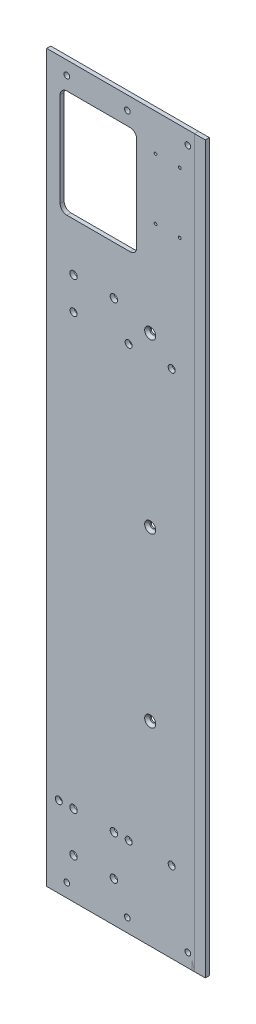
SolidWorks part; units mm, degrees
material "Thornel Mat VMA"
ref_plane "Front" through (0, 0, 0) normal (0, 0, 1) x (1, 0, 0)
ref_plane "Top" through (0, 0, 0) normal (0, 1, 0) x (1, 0, 0)
ref_plane "Right" through (0, 0, 0) normal (1, 0, 0) x (0, 0, -1)
sketch "草图1" plane through (0, 0, 0) normal (0, 0, 1) x (1, 0, 0)
  line L1 (-75, -270) -> (75, -270)
  line L2 (-75, -270) -> (-75, 270)
  line L3 (-75, 270) -> (75, 270)
  line L4 (75, -270) -> (75, 270)
  line L5 (-75, -270) -> (75, 270) construction
  line L6 (-75, 270) -> (75, -270) construction
  point P0 (0, 0)
  dimension "D1" = 150
  dimension "D2" = 540
extrude "凸台-拉伸1" add sketch "草图1" along normal blind 3
sketch "草图2" plane through (0, 0, 0) normal (0, 0, -1) x (-1, 0, 0)
  line L0 (-75, 0) -> (75, 0) construction
  line L1 (-75, -270) -> (-75, 270) construction
  line L2 (75, 270) -> (75, -270) construction
  line L3 (75, -270) -> (-75, -270) construction
  line L4 (0, -270) -> (0, -312.3628) construction
  line L5 (0, 270) -> (0, 297.7999) construction
  line L6 (-75, 270) -> (75, 270) construction
  circle A2 centre (65, -260) radius 2.1
  circle A3 centre (-70, -260) radius 2.1
  circle A6 centre (65, 260) radius 2.1
  circle A7 centre (-70, 260) radius 2.1
  circle A8 centre (-25, -260) radius 2.1
  circle A9 centre (20, -260) radius 2.1
  circle A10 centre (20, 260) radius 2.1
  circle A11 centre (-25, 260) radius 2.1
  circle A16 centre (15, 196.5) radius 1.6
  circle A17 centre (15, 188.5) radius 1.6
  circle A18 centre (-15, 196.5) radius 1.6
  circle A19 centre (-15, 188.5) radius 1.6
  dimension "D2" = 45
  dimension "D3" = 3.2
  dimension "D4" = 4.2
  dimension "D5" = 10
  dimension "D6" = 10
  dimension "D7" = 4.2
  dimension "D8" = 5
  dimension "D9" = 10
  dimension "D10" = 30
  dimension "D11" = 8
  dimension "D12" = 73.5
  dimension "D13" = 45
extrude "切除-拉伸1" cut sketch "草图2" against normal through all
sketch "草图3" plane through (0, 0, 3) normal (0, 0, 1) x (1, 0, 0)
  line L1 (75, -270) -> (75, 270) construction
  circle A0 centre (65, 30) radius 1.5
  circle A1 centre (65, -30) radius 1.5
  dimension "D1" = 3
  dimension "D2" = 10
  dimension "D3" = 30
  dimension "D4" = 3
  dimension "D5" = 30
  dimension "D6" = 10
sketch "草图4" plane through (0, 0, 3) normal (0, 0, 1) x (1, 0, 0)
  line L0 (42, 0) -> (140.7159, 0) construction
  line L1 (75, -270) -> (75, 270) construction
  line L2 (0, 270) -> (0, -270) construction
  line L3 (75, 270) -> (-75, 270) construction
  line L4 (-75, -270) -> (75, -270) construction
  line L5 (-42, 0) -> (-140.7159, 0) construction
  circle A0 centre (42, 125) radius 2.1
  circle A1 centre (42, -125) radius 2.1
  circle A2 centre (42, 0) radius 2.1
  circle A3 centre (-42, 0) radius 2.1
  circle A4 centre (-42, -125) radius 2.1
  circle A5 centre (-42, 125) radius 2.1
  dimension "D1" = 250
  dimension "D2" = 4.2
  dimension "D3" = 4.2
  dimension "D4" = 33
  dimension "D5" = 33
extrude "切除-拉伸2" cut sketch "草图4" against normal up to next
chamfer "倒角1" distance 2 angle 45 3 edges at (44.1, 0, 3) (39.9, -125, 3) (44.1, 125, 3)
sketch "草图6" plane through (0, 0, 3) normal (0, 0, 1) x (1, 0, 0)
  line L0 (0, -286.6484) -> (0, 69.1326) construction
  line L1 (-75, -270) -> (75, -270) construction
  line L2 (-75, 270) -> (-75, -270) construction
  line L3 (75, -270) -> (75, 270) construction
  line L6 (75, 270) -> (-75, 270) construction
  circle A1 centre (26, -210) radius 2.6
  circle A4 centre (-26, -210) radius 2.6
  circle A5 centre (58, -210) radius 2.6
  circle A6 centre (-58, -210) radius 2.6
  circle A9 centre (-47, 110) radius 2.6
  circle A10 centre (-15, 110) radius 2.6
  circle A11 centre (26, 110) radius 2.6
  circle A12 centre (58, 110) radius 2.6
  dimension "D1" = 5.2
  dimension "D2" = 17
  dimension "D3" = 60
  dimension "D4" = 32
  dimension "D5" = 5.2
  dimension "D6" = 5.2
  dimension "D7" = 5.2
  dimension "D8" = 5.2
  dimension "D9" = 32
  dimension "D10" = 17
  dimension "D11" = 32
  dimension "D12" = 28
  dimension "D14" = 160
  dimension "D15" = 160
  dimension "D16" = 160
extrude "切除-拉伸4" cut sketch "草图6" against normal up to next
sketch "草图7" plane through (0, 0, 3) normal (0, 0, 1) x (1, 0, 0)
  line L4 (75, -270) -> (75, 270)
  line L5 (75, 270) -> (-75, 270)
  line L6 (-75, 270) -> (-75, -270)
  line L7 (-75, -270) -> (75, -270)
  line L8 (75, -270) -> (75, 270)
  line L9 (75, 270) -> (-75, 270)
  line L10 (-75, 270) -> (-75, -270)
  line L11 (-75, -270) -> (75, -270)
  circle A2 centre (-15, 134) radius 2.75
  circle A3 centre (15, 134) radius 2.75
  dimension "D2" = 136
  dimension "D3" = 5.5
  dimension "D5" = 30
  dimension "D6" = 5.5
  dimension "D7" = 60
  dimension "D4" = 136
  dimension "D1" = 0
extrude "切除-拉伸5" cut sketch "草图7" against normal up to next contours A2 | A3 region at (-15, 134, 3)
sketch "草图8" plane through (0, 0, 3) normal (0, 0, 1) x (1, 0, 0)
  line L4 (75, -270) -> (75, 270)
  line L5 (75, 270) -> (-75, 270)
  line L6 (-75, 270) -> (-75, -270)
  line L7 (-75, -270) -> (75, -270)
  line L8 (75, -270) -> (75, 270)
  line L9 (75, 270) -> (-75, 270)
  line L10 (-75, 270) -> (-75, -270)
  line L11 (-75, -270) -> (75, -270)
  circle A2 centre (-15, -210) radius 2.75
  circle A3 centre (15, -210) radius 2.75
  dimension "D2" = 5.5
  dimension "D3" = 5.5
  dimension "D4" = 30
  dimension "D5" = 60
  dimension "D6" = 60
  dimension "D7" = 60
  dimension "D1" = 0
extrude "切除-拉伸6" cut sketch "草图8" against normal up to next contours A2 | A3 region at (-15, -210, 3) region at (15, -210, 3)
sketch "草图9" plane through (0, 0, 3) normal (0, 0, 1) x (1, 0, 0)
  line L0 (0, -270) -> (0, -79.9483) construction
  line L1 (-75, -270) -> (75, -270) construction
  circle A0 centre (-15, -240) radius 2.75
  circle A1 centre (15, -240) radius 2.75
  dimension "D1" = 5.5
  dimension "D2" = 30
  dimension "D3" = 30
extrude "切除-拉伸7" cut sketch "草图9" against normal blind 10
sketch "草图10" plane through (0, 0, 3) normal (0, 0, 1) x (1, 0, 0)
  line L0 (0, 270) -> (0, 151.6479) construction
  line L1 (75, 270) -> (-75, 270) construction
  line L2 (-25, 170) -> (-25, 250)
  line L3 (-25, 170) -> (25, 170)
  line L4 (0, 170) -> (0, 250)
  line L5 (-25, 250) -> (25, 250)
  line L6 (25, 170) -> (25, 250)
  line L8 (25, 250) -> (32, 250)
  line L9 (25, 250) -> (25, 170)
  line L10 (25, 170) -> (32, 170)
  line L11 (32, 250) -> (32, 170)
  circle M23 centre (-15, 196.5) radius 1.6
  circle M28 centre (15, 188.5) radius 1.6
  circle M29 centre (15, 196.5) radius 1.6
  circle M30 centre (-15, 188.5) radius 1.6
  dimension "D1" = 50
  dimension "D2" = 20
  dimension "D3" = 80
  dimension "D4" = 7
extrude "切除-拉伸8" cut sketch "草图10" against normal blind 10 contours L5 L2 L3 L4 M30 M23 | L3 L6 L5 L4 M28 M29 | L11 L8 L6 L10 region at (-12.4797, 210.1419, 3) region at (12.4797, 210.1419, 3) region at (28.5, 210, 3)
fillet "圆角1" radius 5 4 edges at (-25, 170, 1.5) (-25, 250, 1.5) (32, 170, 1.5) (32, 250, 1.5)
sketch "草图11" plane through (0, 0, 3) normal (0, 0, 1) x (1, 0, 0)
  line L0 (55, 266.5246) -> (55, 192.9358) construction
  line L1 (-66.7226, 220) -> (-27.8973, 220) construction
  line L2 (-75, 270) -> (-75, -270) construction
  line L3 (75, 270) -> (-75, 270) construction
  circle A0 centre (46, 242.6) radius 1
  circle A1 centre (64, 242.6) radius 1
  circle A2 centre (64, 197.4) radius 1
  circle A3 centre (46, 197.4) radius 1
  dimension "D1" = 2
  dimension "D2" = 18
  dimension "D3" = 45.2
  dimension "D4" = 130
  dimension "D5" = 50
extrude "切除-拉伸9" cut sketch "草图11" against normal blind 4
sketch "草图13" plane through (0, 0, 3) normal (0, 0, 1) x (1, 0, 0)
  line L0 (-35, 270) -> (-35, -270)
  line L1 (75, 270) -> (-75, 270) construction
  line L2 (-75, -270) -> (75, -270) construction
  line L4 (-35, 270) -> (-236.483, 270)
  line L5 (-35, 270) -> (-35, -387.7593)
  line L6 (-35, -387.7593) -> (-236.483, -387.7593)
  line L7 (-236.483, 270) -> (-236.483, -387.7593)
  circle A0 centre (-20, 260) radius 2.1 construction
  line M10 (75, 270) -> (-75, 270)
  line M11 (-75, 270) -> (-75, -270)
  line M12 (-75, -270) -> (75, -270)
  circle M16 centre (-65, -260) radius 2.1
  circle M20 centre (-65, 260) radius 2.1
  circle M27 centre (-47, 110) radius 2.6
  circle M28 centre (-58, -210) radius 2.6
  dimension "D1" = 15
extrude "切除-拉伸10" cut sketch "草图13" against normal blind 10 contours L0 M10 M11 M12 M16 M20 M28 M27 region at (-54.9921, 0.0986, 3)
sketch "草图14" plane through (0, 0, 3) normal (0, 0, 1) x (1, 0, 0)
  line L0 (-35, -270) -> (75, -270) construction
  line L1 (73, 270) -> (83, 270)
  line L2 (73, 270) -> (73, -270)
  line L3 (73, -270) -> (83, -270)
  line L4 (83, 270) -> (83, -270)
  line L5 (75, -270) -> (75, 270) construction
  point P7 (75, 270)
  dimension "D1" = 10
  dimension "D2" = 2
extrude "凸台-拉伸2" add sketch "草图14" against normal blind 3 separate body
